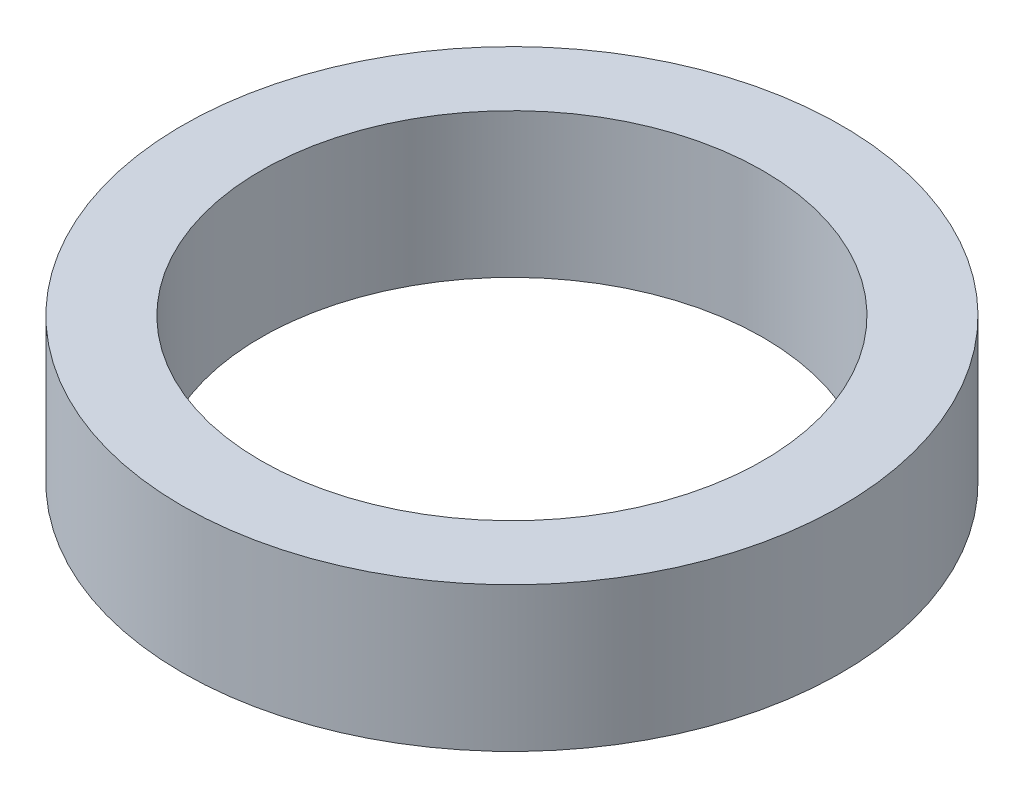
SolidWorks part; units mm, degrees
ref_plane "Front Plane" through (0, 0, 0) normal (0, 0, 1) x (1, 0, 0)
ref_plane "Top Plane" through (0, 0, 0) normal (0, 1, 0) x (1, 0, 0)
ref_plane "Right Plane" through (0, 0, 0) normal (1, 0, 0) x (0, 0, -1)
sketch "Sketch1" plane through (0, 0, 0) normal (0, 1, 0) x (1, 0, 0)
  circle A0 centre (0, 0) radius 52.5
  dimension "FLANGE_OD" = 105
extrude "Boss-Extrude1" add sketch "Sketch1" along normal blind 23
sketch "Sketch2" plane through (0, 0, 0) normal (0, 1, 0) x (1, 0, 0)
  circle A0 centre (0, 0) radius 40
  dimension "BORE_D" = 80
extrude "Cut-Extrude1" cut sketch "Sketch2" along normal through all
sketch "Sketch3" plane through (0, 23, 0) normal (0, 1, 0) x (1, 0, 0)
  circle A0 centre (0, 0) radius 23.5445 construction
  circle A1 centre (-23.5445, 0) radius 1.8386
  dimension "BOLT_D" = 3.6772
  dimension "BOLT_PCD" = 47.089
extrude "Cut-Extrude2" cut sketch "Sketch3" against normal blind 17.5876 rebuild error yes
pattern_circular "CirPattern1" count 6 over 360 rebuild error yes
